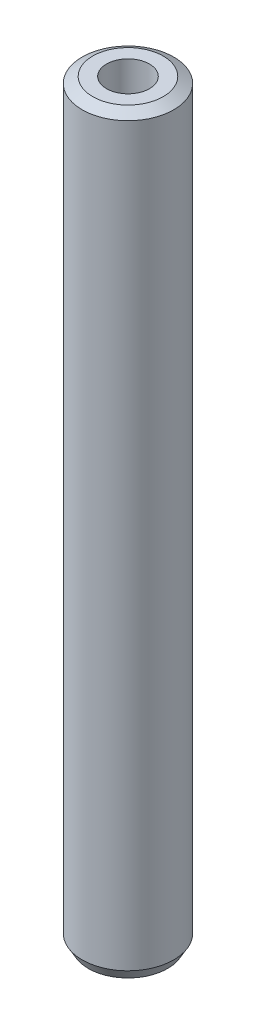
SolidWorks part; units mm, degrees
ref_plane "Front Plane" through (0, 0, 0) normal (0, 0, 1) x (1, 0, 0)
ref_plane "Top Plane" through (0, 0, 0) normal (0, 1, 0) x (1, 0, 0)
ref_plane "Right Plane" through (0, 0, 0) normal (1, 0, 0) x (0, 0, -1)
sketch "Sketch1" plane through (0, 0, 0) normal (0, 1, 0) x (1, 0, 0)
  circle A0 centre (0, 0) radius 10
  dimension "SHAFT_OD" = 20
extrude "Boss-Extrude1" add sketch "Sketch1" along normal blind 164.4827
sketch "Sketch2" plane through (0, 0, 0) normal (0, 1, 0) x (1, 0, 0)
  circle A0 centre (0, 0) radius 4.686
  dimension "BORE_D" = 9.372
extrude "Cut-Extrude1" cut sketch "Sketch2" along normal through all
chamfer "Chamfer1" distance 1.3291 angle 60 2 edges at (0, 164.4827, 10) (0, 0, 10) first distance on face at (0, 164.4827, 10) first distance on face at (0, 0, 4.686)
